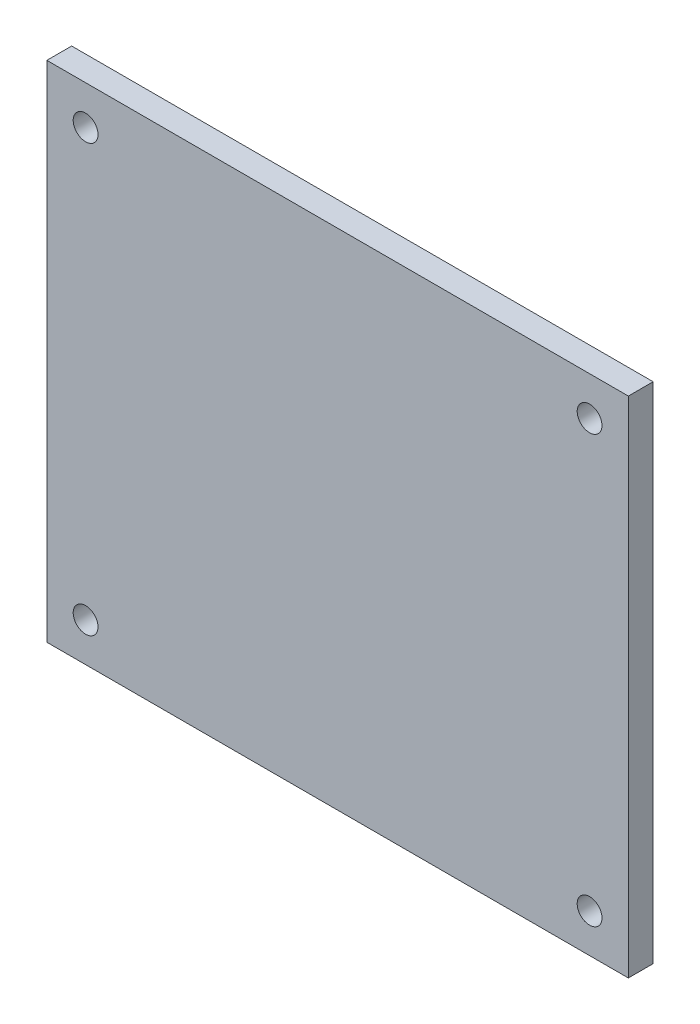
SolidWorks part; units mm, degrees
material "Pine"
ref_plane "Front Plane" through (0, 0, 0) normal (0, 0, 1) x (1, 0, 0)
ref_plane "Top Plane" through (0, 0, 0) normal (0, 1, 0) x (1, 0, 0)
ref_plane "Right Plane" through (0, 0, 0) normal (1, 0, 0) x (0, 0, -1)
sketch "Sketch1" plane through (0, 0, 0) normal (0, 0, 1) x (1, 0, 0)
  line L1 (37.5, 32.5) -> (-37.5, 32.5)
  line L2 (37.5, 32.5) -> (37.5, -32.5)
  line L3 (37.5, -32.5) -> (-37.5, -32.5)
  line L4 (-37.5, 32.5) -> (-37.5, -32.5)
  line L5 (37.5, 32.5) -> (-37.5, -32.5) construction
  line L6 (37.5, -32.5) -> (-37.5, 32.5) construction
  point P0 (0, 0)
  dimension "D1" = 65
  dimension "D2" = 75
base flange "Base-Flange1" sketch "Sketch1" thickness 3.2 reverse thickness direction no parameters "D1"=7.366
hole_wizard "Ø3.2 (3.2) Diameter Hole1" positions "Sketch6" profile "Sketch7" hole size "Ø3.2" standard "ISO" end condition through all
sketch "Sketch6" plane through (0, 0, 0) normal (0, 0, 1) x (1, 0, 0)
  line L1 (32.5, 27.5) -> (-32.5, 27.5) construction
  line L2 (32.5, 27.5) -> (32.5, -27.5) construction
  line L3 (32.5, -27.5) -> (-32.5, -27.5) construction
  line L4 (-32.5, 27.5) -> (-32.5, -27.5) construction
  line L5 (32.5, 27.5) -> (-32.5, -27.5) construction
  line L6 (32.5, -27.5) -> (-32.5, 27.5) construction
  point P0 (-32.5, 27.5)
  point P2 (-32.5, -27.5)
  point P4 (32.5, -27.5)
  point P6 (32.5, 27.5)
  dimension "D1" = 55
  dimension "D2" = 65
sketch "Sketch7" plane through (-32.5, 27.5, 0) normal (1, 0, 0) x (0, -1, 0)
  line L0 (0, 0) -> (0, 3.2)
  line L1 (0, 3.2) -> (1.6, 3.2)
  line L2 (1.6, 3.2) -> (1.6, 0)
  line L5 (1.6, 0) -> (0, 0)
  line L11 (0, -6.35) -> (0, 107.95) construction
  dimension "Thru Hole Dia." = 3.2
  dimension "Thru Hole Depth" = 3.2
sketch "Bend-Lines1" [suppressed] plane through (0, 0, 0) normal (0, 1, 0) x (1, 0, 0)
sketch "Bounding-Box1" [suppressed] plane through (0, 0, 0) normal (0, 1, 0) x (1, 0, 0)
sheet metal parameters "Sheet-Metal1" thickness 3.2 parameters "D1"=7.366
flat pattern "Flat-Pattern1" [suppressed]
sketch "Bend-Lines2" plane through (0, 0, 0) normal (0, 1, 0) x (1, 0, 0)
sketch3d "Bounding-Box2" [suppressed]
  line L0 (37.5, -32.5, 0) -> (-37.5, -32.5, 0) construction
  line L1 (37.5, 32.5, 0) -> (-37.5, 32.5, 0) construction
  line L2 (37.5, -32.5, 0) -> (37.5, 32.5, 0) construction
  line L3 (-37.5, -32.5, 0) -> (-37.5, 32.5, 0) construction
sheet metal parameters "Sheet-Metal2" thickness 3.2 parameters "D1"=7.366
flat pattern "Flat-Pattern1"
sketch "Bend-Lines2" plane through (0, 0, 0) normal (0, 1, 0) x (1, 0, 0)
sketch3d "Bounding-Box2" [suppressed]
  line L0 (-37.5, -32.5, 0) -> (37.5, -32.5, 0) construction
  line L1 (-37.5, 32.5, 0) -> (37.5, 32.5, 0) construction
  line L2 (-37.5, -32.5, 0) -> (-37.5, 32.5, 0) construction
  line L3 (37.5, -32.5, 0) -> (37.5, 32.5, 0) construction
